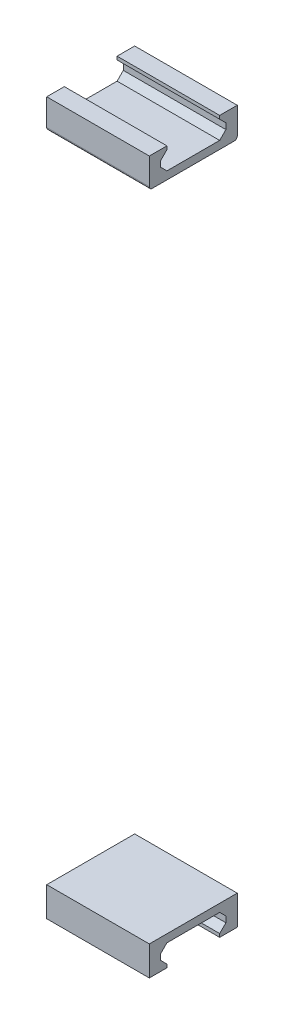
SolidWorks part; units mm, degrees
ref_plane "Front Plane" through (0, 0, 0) normal (1, 0, 0) x (0, 1, 0)
ref_plane "Top Plane" through (0, 0, 0) normal (0, 0, 1) x (0, 1, 0)
ref_plane "Right Plane" through (0, 0, 0) normal (0, 1, 0) x (-1, 0, 0)
sketch "Sketch1" plane through (0, 0, 0) normal (1, 0, 0) x (0, 1, 0)
  line L0 (60.1161, 26.3922) -> (61.2508, 26.3922)
  line L1 (60.1161, 8.3892) -> (61.2508, 8.3892)
  line L2 (53.8622, 26.3922) -> (53.8622, 8.3892)
  line L3 (53.8622, 8.3892) -> (55.9854, 6.266)
  line L4 (55.9854, 6.266) -> (57.9929, 6.266)
  line L5 (57.9929, 6.266) -> (60.1161, 8.3892)
  line L12 (53.8622, 17.3907) -> (73.2887, 17.3907) construction
  line L20 (57.9929, 28.5154) -> (60.1161, 26.3922)
  line L21 (55.9854, 28.5154) -> (57.9929, 28.5154)
  line L22 (53.8622, 26.3922) -> (55.9854, 28.5154)
  line L23 (61.2508, 26.3922) -> (61.2508, 32.3922)
  line L24 (61.2508, 32.3922) -> (51.1805, 32.3922)
  line L25 (51.1805, 32.3922) -> (51.1805, 2.3892)
  line L26 (51.1805, 2.3892) -> (61.2508, 2.3892)
  line L27 (61.2508, 2.3892) -> (61.2508, 8.3892)
extrude "Boss-Extrude1" add sketch "Sketch1" along normal blind 35
ref_plane "Plane2" through (0, -60.1778, 0) normal (0, 1, 0) x (1, 0, 0)
mirror "Mirror4" about plane through (0, -60.1778, 0) normal (0, 1, 0) of bodies 101
fillet "Fillet1" radius 1 2 edges at (17.5, 51.1805, 2.3892) (17.5, 51.1805, 32.3922)
